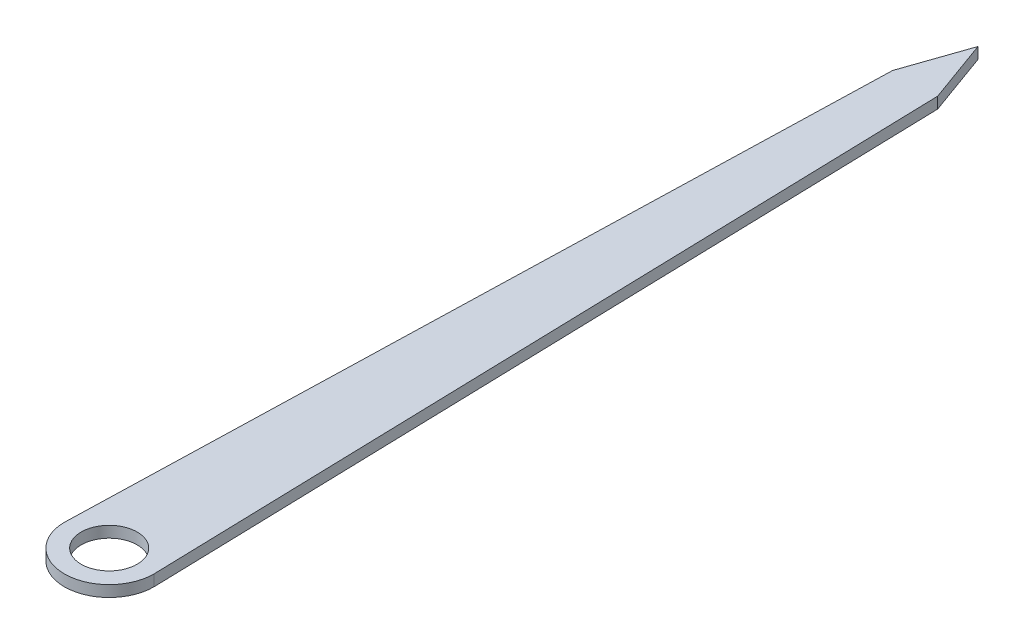
SolidWorks part; units mm, degrees
ref_plane "Přední rovina" through (0, 0, 0) normal (0, 0, 1) x (1, 0, 0)
ref_plane "Horní rovina" through (0, 0, 0) normal (0, 1, 0) x (1, 0, 0)
ref_plane "Pravá rovina" through (0, 0, 0) normal (1, 0, 0) x (0, 0, -1)
sketch "Skica1" plane through (0, 0, 0) normal (0, 1, 0) x (1, 0, 0)
  line L5 (25, 30) -> (195, 30)
  line L6 (0, 0) -> (220, 0)
  line L7 (0, 0) -> (0, 160)
  line L8 (0, 160) -> (220, 160)
  line L9 (220, 0) -> (220, 160)
  line L14 (106, 34) -> (108.0409, 105.9711)
  line L15 (108.0409, 105.9711) -> (110, 111.6422)
  line L16 (114, 34) -> (112.0409, 106)
  line L17 (112.0409, 106) -> (110, 111.6422)
  arc A1 (25, 30) -> (195, 30) centre (110, 30) cw
  circle A2 centre (110, 34) radius 2
  circle A3 centre (110, 34) radius 4
  point P6 (96.8851, 113.9821)
  point P8 (29.0741, 56)
  point P9 (41.2614, 80)
  point P10 (59, 98)
  point P11 (84.2318, 111)
  point P12 (135.7682, 111)
  point P13 (161, 98)
  point P14 (178.7386, 80)
  point P15 (190.9259, 56)
  point P16 (110, 115)
  point P17 (26, 43)
  point P19 (34.4752, 69)
  point P20 (49.69, 89.8974)
  point P21 (69.966, 104.9819)
  point P22 (122.9619, 114.0059)
  point P23 (147.8188, 106.1232)
  point P24 (170.7731, 89.4275)
  point P25 (185.5594, 68.933)
  point P26 (193.9442, 43.3553)
  dimension "D3" = 85
  dimension "D13" = 68
  dimension "D25" = 4
  dimension "D26" = 8
  dimension "D1" = 160
  dimension "D2" = 220
  dimension "D4" = 25
  dimension "D5" = 25
  dimension "D6" = 30
  dimension "D7" = 26
  dimension "D8" = 50
  dimension "D9" = 68
  dimension "D10" = 81
  dimension "D11" = 26
  dimension "D12" = 50
  dimension "D14" = 81
  dimension "D15" = 13
  dimension "D16" = 13
  dimension "D17" = 13
  dimension "D18" = 13
  dimension "D19" = 13
  dimension "D20" = 13
  dimension "D21" = 13
  dimension "D22" = 13
  dimension "D23" = 13
  dimension "D24" = 13
  dimension "D27" = 72
  dimension "D28" = 6
  dimension "D29" = 72
  dimension "D30" = 6
  dimension "D31" = 0
  dimension "D32" = 0
  dimension "D33" = 4
  dimension "D34" = 4
  dimension "D35" = 85
extrude "Přidat vysunutím3" add sketch "Skica1" along normal blind 2 contours A3 L16 L17 L15 L14 | A3 L16 L14 A2 region at (107.2516, 0, -31.2516) region at (110.0198, 0, -68.9479)
sketch "Skica5" plane through (0, 2, 0) normal (0, 1, 0) x (1, 0, 0)
  circle A0 centre (110, 34) radius 4
  circle A1 centre (110, 34) radius 2
  circle A2 centre (110, 34) radius 2.5
  circle M6 centre (110, 34) radius 2
  dimension "D1" = 8
  dimension "D2" = 4
  dimension "D3" = 5
extrude "Odebrat vysunutím1" cut sketch "Skica5" against normal blind 18 contours A2 M6 region at (107.5707, 2, -34)
sketch "Skica14" plane through (0, 2, 0) normal (0, 1, 0) x (1, 0, 0)
extrude "Odebrat vysunutím3" cut sketch "Skica1<6>" along normal blind 1 contours A3 L16 L17 L15 L14 | A3 L16 L14 A2 region at (107.2516, 0, -31.2516) region at (110.0198, 0, -68.9479)
sketch "Skica1<6>" plane through (0, 0, 0) normal (0, 1, 0) x (1, 0, 0) same geometry as "Skica1"
